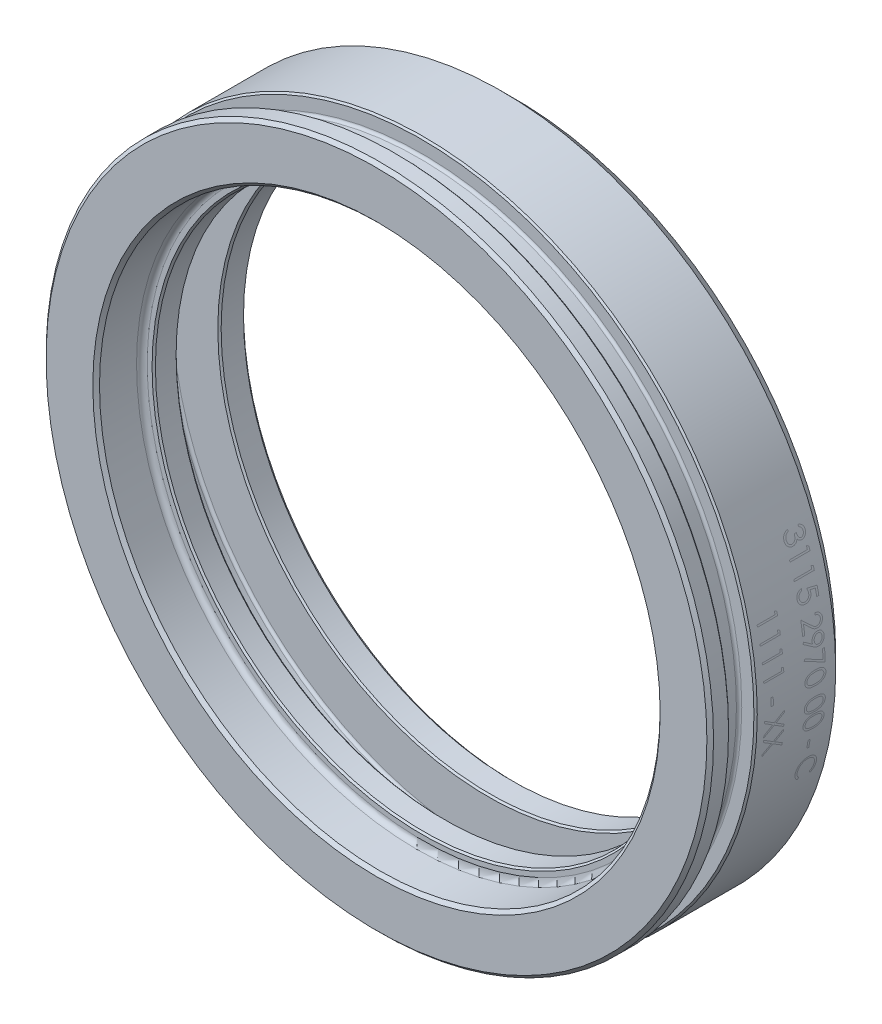
SolidWorks part; units mm, degrees
material "4140 H/T"
ref_plane "Front Plane" through (0, 0, 0) normal (0, 0, 1) x (1, 0, 0)
ref_plane "Top Plane" through (0, 0, 0) normal (0, 1, 0) x (1, 0, 0)
ref_plane "Right Plane" through (0, 0, 0) normal (1, 0, 0) x (0, 0, -1)
sketch "Sketch1" plane through (0, 0, 0) normal (1, 0, 0) x (0, 0, -1)
  line L0 (-12.2825, 0) -> (113.0836, 0) construction
  line L1 (0, 49.5) -> (0, 42.5)
  line L2 (0.5, 42) -> (6.05, 42)
  line L3 (6.85, 41.2) -> (6.85, 40.475)
  line L4 (7.1, 40.225) -> (10.2, 40.225)
  line L5 (10.45, 40.475) -> (10.45, 47.35)
  line L6 (10.85, 47.75) -> (16.3, 47.75)
  line L7 (16.7, 47.35) -> (16.7, 40.475)
  line L8 (16.95, 40.225) -> (20.3, 40.225)
  line L9 (20.8, 40.725) -> (20.8, 48)
  line L12 (18.8, 50) -> (7.05, 50)
  line L13 (6.8, 49.75) -> (6.8, 47.925)
  line L14 (6.4, 47.525) -> (3.4, 47.525)
  line L15 (3, 47.925) -> (3, 49.75)
  line L16 (2.75, 50) -> (0.5, 50)
  line L17 (0, 42.5) -> (0.5, 42)
  line L18 (0.5, 50) -> (0, 49.5)
  line L19 (20.3, 40.225) -> (20.8, 40.725)
  line L20 (20.8, 48) -> (18.8, 50)
  line L21 (3, 49.75) -> (2.75, 50)
  line L22 (7.05, 50) -> (6.8, 49.75)
  line L23 (10.2, 40.225) -> (10.45, 40.475)
  line L24 (16.7, 40.475) -> (16.95, 40.225)
  line L25 (6.85, 40.475) -> (7.1, 40.225)
  arc A0 (6.8, 47.925) -> (6.4, 47.525) centre (6.4, 47.925) cw
  arc A1 (3.4, 47.525) -> (3, 47.925) centre (3.4, 47.925) cw
  arc A2 (16.3, 47.75) -> (16.7, 47.35) centre (16.3, 47.35) cw
  arc A3 (10.45, 47.35) -> (10.85, 47.75) centre (10.85, 47.35) cw
  arc A4 (6.05, 42) -> (6.85, 41.2) centre (6.05, 41.2) cw
  point P4 (0, 42)
  point P6 (6.85, 40.225)
  point P7 (10.45, 40.225)
  point P10 (16.7, 40.225)
  point P15 (6.8, 50)
  point P18 (3, 50)
  point P19 (0, 50)
  point P23 (20.8, 40.225)
  point P29 (6.8, 47.525)
  point P32 (3, 47.525)
  point P39 (16.7, 47.75)
  point P42 (10.45, 47.75)
  dimension "D24" = 0.4
  dimension "D25" = 0.4
  dimension "D26" = 0.8
  dimension "D1" = 80.45
  dimension "D3" = 95.5
  dimension "D4" = 100
  dimension "D5" = 45
  dimension "D6" = 20.8
  dimension "D7" = 6.8
  dimension "D8" = 3.8
  dimension "D9" = 84
  dimension "D10" = 95.05
  dimension "D11" = 16.7
  dimension "D12" = 6.25
  dimension "D13" = 2
  dimension "D14" = 0.5
  dimension "D15" = 45
  dimension "D16" = 0.5
  dimension "D17" = 45
  dimension "D18" = 0.5
  dimension "D19" = 45
  dimension "D22" = 3.6
  dimension "D23" = 6.85
revolve "Revolve1" add sketch "Sketch1" angle 360 about L0
sketch "Sketch2" plane through (0, 0, 0) normal (1, 0, 0) x (0, 0, -1)
  line L0 (14.2566, 37.9303) -> (14.2566, -32.669) construction
  text T0 "3115 2970 00 - C\r\n1111 - XX" font "Century Gothic" height 3
  dimension "D1" = 14.2566
wrap "Wrap1" sketch "Sketch2" wrap type scribe source sketch "Sketch2" face at (50, 0, -7.05)
